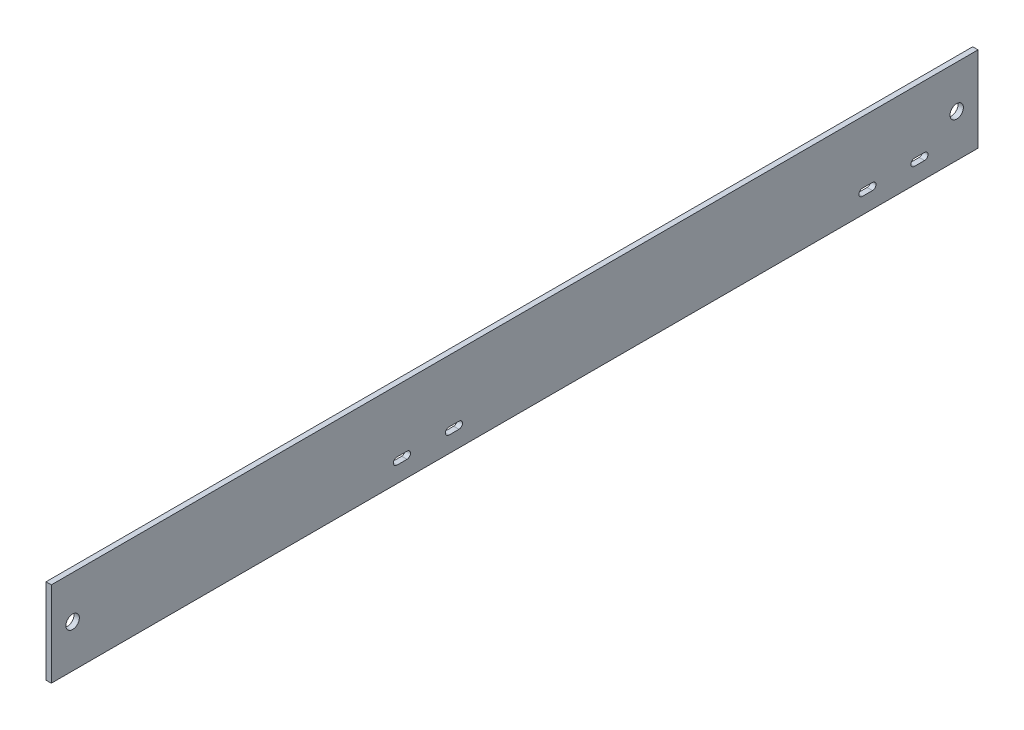
SolidWorks part; units mm, degrees
ref_plane "Front Plane" through (0, 0, 0) normal (0, 0, 1) x (1, 0, 0)
ref_plane "Top Plane" through (0, 0, 0) normal (0, 1, 0) x (1, 0, 0)
ref_plane "Right Plane" through (0, 0, 0) normal (1, 0, 0) x (0, 0, -1)
sketch "Sketch1" plane through (0, 0, 0) normal (1, 0, 0) x (0, 0, -1)
  line L0 (206.025, 11.7) -> (212.025, 11.7) construction
  line L1 (0, 0) -> (552.45, 0)
  line L2 (0, 0) -> (0, 50.8)
  line L3 (0, 50.8) -> (552.45, 50.8)
  line L4 (552.45, 0) -> (552.45, 50.8)
  line L5 (206.025, 13.8) -> (212.025, 13.8)
  line L6 (206.025, 9.6) -> (212.025, 9.6)
  line L7 (237.025, 11.7) -> (243.025, 11.7) construction
  line L8 (237.025, 13.8) -> (243.025, 13.8)
  line L9 (237.025, 9.6) -> (243.025, 9.6)
  line L10 (483.55, 11.7) -> (489.55, 11.7) construction
  line L11 (483.55, 13.8) -> (489.55, 13.8)
  line L12 (483.55, 9.6) -> (489.55, 9.6)
  line L13 (514.55, 11.7) -> (520.55, 11.7) construction
  line L14 (514.55, 13.8) -> (520.55, 13.8)
  line L15 (514.55, 9.6) -> (520.55, 9.6)
  circle A0 centre (12.7, 25.4) radius 4
  circle A1 centre (539.75, 25.4) radius 4
  arc A2 (206.025, 13.8) -> (206.025, 9.6) centre (206.025, 11.7) ccw
  arc A3 (212.025, 9.6) -> (212.025, 13.8) centre (212.025, 11.7) ccw
  arc A4 (237.025, 13.8) -> (237.025, 9.6) centre (237.025, 11.7) ccw
  arc A5 (243.025, 9.6) -> (243.025, 13.8) centre (243.025, 11.7) ccw
  arc A8 (483.55, 13.8) -> (483.55, 9.6) centre (483.55, 11.7) ccw
  arc A9 (489.55, 9.6) -> (489.55, 13.8) centre (489.55, 11.7) ccw
  arc A10 (514.55, 13.8) -> (514.55, 9.6) centre (514.55, 11.7) ccw
  arc A11 (520.55, 9.6) -> (520.55, 13.8) centre (520.55, 11.7) ccw
  point P11 (209.025, 11.7)
  point P16 (240.025, 11.7)
  point P29 (486.55, 11.7)
  point P34 (517.55, 11.7)
  dimension "D3" = 8
  dimension "D8" = 4.2
  dimension "D1" = 50.8
  dimension "D2" = 552.45
  dimension "D4" = 25.4
  dimension "D5" = 12.7
  dimension "D6" = 12.7
  dimension "D7" = 6
  dimension "D9" = 31
  dimension "D10" = 39.1
  dimension "D11" = 209.025
  dimension "D12" = 240.025
  dimension "D13" = 539.75
  dimension "D19" = 31
  dimension "D20" = 34.9
extrude "Boss-Extrude2" add sketch "Sketch1" along normal blind 3.175
equation "\"RailThickness\"= .125in'Spec"
equation "\"VSWidth\"= 1.25in'Spec"
equation "\"SideRailLength\"= 21.75in"
equation "\"LowerRailHeight\"= 2.0in"
equation "\"StepperHolePadSize\"= \"StepperHoleDiameter\""
equation "\"DistanceFromFrontSideToFirstLeftStepperHoleMountYSValue\"= 74.025mm"
equation "\"DistanceBetweenFrontToBackStepperHoles\"= \"BedLength\" - \"BuildPlateStandoffHolesDistanceFromFrontOrBackSide\" * 2'Equals 270"
equation "\"BedLength\"= \"BuildPlateLength\""
equation "\"D1@Sketch1\"=\"LowerRailHeight\""
equation "\"D2@Sketch1\"=\"SideRailLength\""
equation "\"FrameFastenerHoleDiameter\"= 8mm"
equation "\"D3@Sketch1\"=\"FrameFastenerHoleDiameter\""
equation "\"D4@Sketch1\"=\"LowerRailHeight\"/2"
equation "\"D5@Sketch1\"=\"FrameFastenerHoleOffsetFromEdge\""
equation "\"D6@Sketch1\"=\"FrameFastenerHoleOffsetFromEdge\""
equation "\"D8@Sketch1\"=\"StepperMountSlotDiameterOnRails\""
equation "\"D1@Boss-Extrude2\"=\"RailThickness\""
equation "\"FrameFastenerHoleOffsetFromEdge\"= \"VSWidth\" / 2 - \"GapBetweenVerticalSupportsAndRails\" / 2"
equation "\"StepperMountSlotDiameterOnRails\"= 4.2mm"
equation "\"StepperMountSlotWidth\"= 6mm"
equation "\"Nema17StepperMountSlotDistance\"= 31mm'Spec"
equation "\"D9@Sketch1\"=\"Nema17StepperMountSlotDistance\""
equation "\"D7@Sketch1\"=\"StepperMountSlotWidth\""
equation "\"BuildPlateLength\"= 352mm'Spec"
equation "\"BuildPlateStandoffHolesDistanceFromFrontOrBackSide\"= 41mm"
equation "\"D10@Sketch1\"=\"OffsetToGive10mmZAxisMovement\""
equation "\"DistanceFromFrontSideToMidRightStepperHoleMount\"= \"DistanceFromFrontSideToFirstLeftStepperHoleMountYSValue\" + \"DistanceBetweenFrontToBackStepperHoles\" / 2'Equals 209.025"
equation "\"D11@Sketch1\"=\"DistanceFromFrontSideToMidRightStepperHoleMount\""
equation "\"OffsetToGive10mmZAxisMovement\"= \"LowerRailHeight\" / 2 + 13.7mm'Allow Stepper 10mm Vertical movement"
equation "\"GapBetweenVerticalSupportsAndRails\"= \"RailThickness\" * 2"
equation "\"AngleBracketSmallHoleDiameter\"= 4mm"
equation "\"AngleBracketSlotDistanceBetweenHoles\"= 30mm"
equation "\"AngleBracketSlotDistanceFromTop\"= 13mm"
equation "\"AngleBracketSlotDistanceFromCorner\"= \"AngleBracketSlotDistanceFromBack\" - \"GapBetweenVerticalSupportsAndRails\" / 2'Equals 61.825"
equation "\"AngleBracketSlotDistanceFromBack\"= 65mm"
equation "\"DistanceFromBackToFirstGantryStepperHole\"= \"VSWidth\" - \"RailThickness\" + ( \"Nema17MountWidth\" - \"Nema17StepperMountSlotDistance\" ) / 2 - \"GapBetweenVerticalSupportsAndRails\" / 2'Equals 34.9. Push Gantry stepper as far back as possible"
equation "\"Nema17MountWidth\"= 50mm"
equation "\"D19@Sketch1\"=\"Nema17StepperMountSlotDistance\""
equation "\"D20@Sketch1\"=\"DistanceFromBackToFirstGantryStepperHole\""
